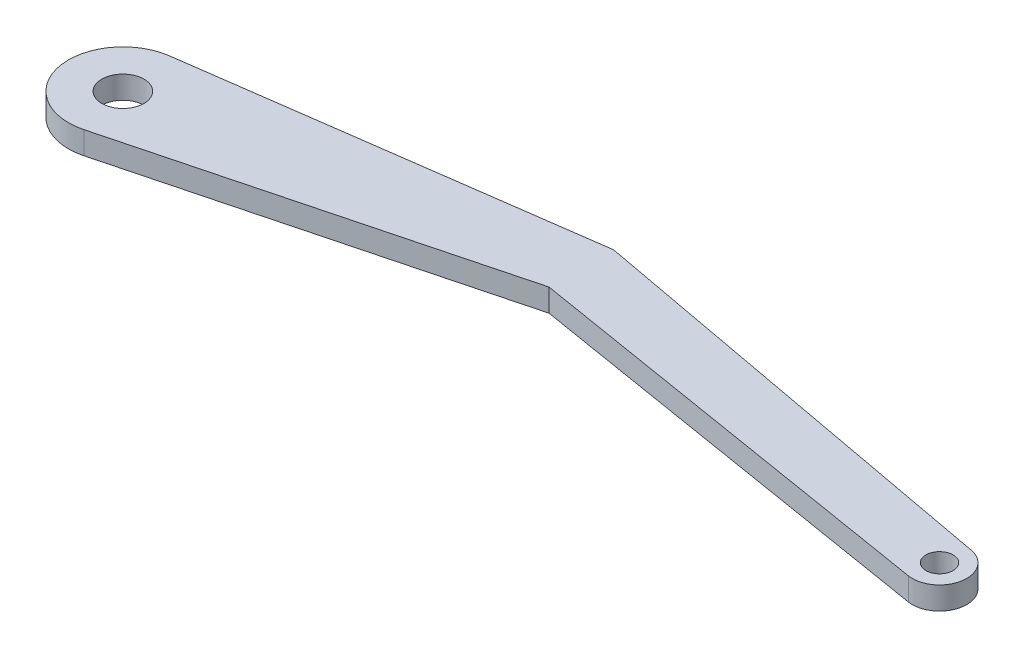
SolidWorks part; units mm, degrees
ref_plane "Front Plane" through (0, 0, 0) normal (0, 0, 1) x (1, 0, 0)
ref_plane "Top Plane" through (0, 0, 0) normal (0, 1, 0) x (1, 0, 0)
ref_plane "Right Plane" through (0, 0, 0) normal (1, 0, 0) x (0, 0, -1)
sketch "Sketch1" plane through (0, 0, 0) normal (0, 1, 0) x (1, 0, 0)
  line L0 (0, 0) -> (180, 0) construction
  line L1 (-1.6499, 11.886) -> (84.3319, 23.8211)
  line L2 (84.3319, 23.8211) -> (181.0927, 5.8997)
  line L3 (3.0285, -11.6116) -> (84.3319, 9.5939)
  line L4 (84.3319, 9.5939) -> (179.0299, -5.9211)
  line L5 (84.3319, 23.8211) -> (84.3319, 9.5939) construction
  line L6 (0, 0) -> (84.3319, 16.7075) construction
  line L7 (84.3319, 16.7075) -> (180, 0) construction
  circle A0 centre (0, 0) radius 4.65
  arc A1 (-1.6499, 11.886) -> (3.0285, -11.6116) centre (0, 0) ccw
  arc A2 (179.0299, -5.9211) -> (181.0927, 5.8997) centre (180, 0) ccw
  dimension "D1" = 9.3
  dimension "D2" = 12
  dimension "D3" = 6
  dimension "D4" = 180
extrude "Boss-Extrude1" add sketch "Sketch1" along normal blind 5 contours A2 A1 A0 region at (41.6177, 0, -15.8606)
sketch "Sketch2" plane through (0, 5, 0) normal (0, 1, 0) x (1, 0, 0)
  circle A0 centre (180, 0) radius 3
  dimension "D1" = 6
extrude "Cut-Extrude1" cut sketch "Sketch2" against normal through all contours A0
